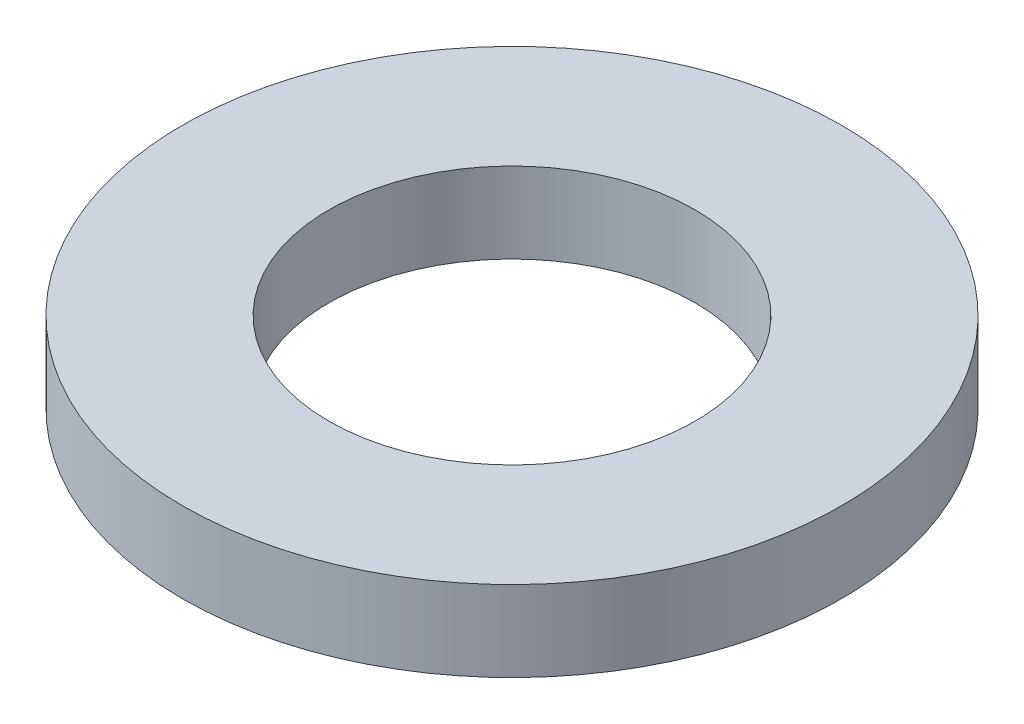
SolidWorks part; units mm, degrees
ref_plane "Front Plane" through (0, 0, 0) normal (0, 0, 1) x (1, 0, 0)
ref_plane "Top Plane" through (0, 0, 0) normal (0, 1, 0) x (1, 0, 0)
ref_plane "Right Plane" through (0, 0, 0) normal (1, 0, 0) x (0, 0, -1)
sketch "Sketch1" plane through (0, 0, 0) normal (0, 1, 0) x (1, 0, 0)
  circle A0 centre (0, 0) radius 45
  dimension "FLANGE_OD" = 90
extrude "Boss-Extrude1" add sketch "Sketch1" along normal blind 11
sketch "Sketch2" plane through (0, 0, 0) normal (0, 1, 0) x (1, 0, 0)
  circle A0 centre (0, 0) radius 25
  dimension "BORE_D" = 50
extrude "Cut-Extrude1" cut sketch "Sketch2" along normal through all
sketch "Sketch3" plane through (0, 11, 0) normal (0, 1, 0) x (1, 0, 0)
  circle A0 centre (0, 0) radius 19.2819 construction
  circle A1 centre (-19.2819, 0) radius 2.3902
  dimension "BOLT_D" = 4.7804
  dimension "BOLT_PCD" = 38.5639
extrude "Cut-Extrude2" cut sketch "Sketch3" against normal blind 10.1796 rebuild error yes
pattern_circular "CirPattern1" count 8 over 360 rebuild error yes
